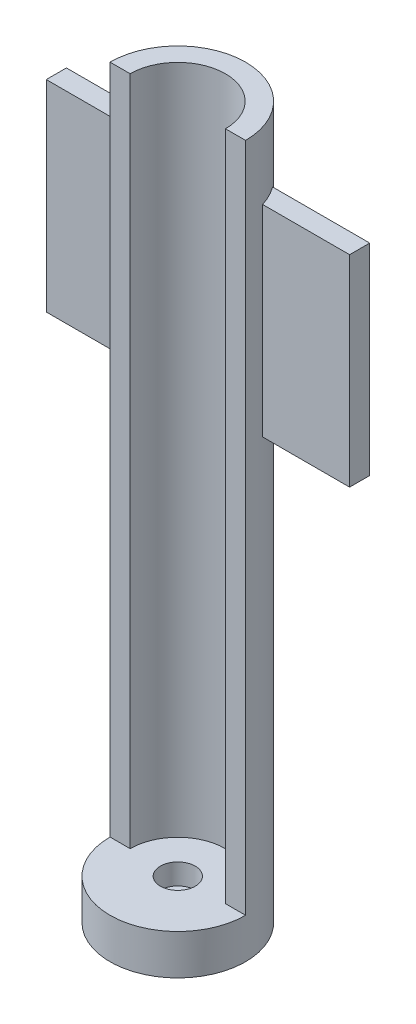
SolidWorks part; units mm, degrees
ref_plane "Front Plane" through (0, 0, 0) normal (0, 0, 1) x (1, 0, 0)
ref_plane "Top Plane" through (0, 0, 0) normal (0, 1, 0) x (1, 0, 0)
ref_plane "Right Plane" through (0, 0, 0) normal (1, 0, 0) x (0, 0, -1)
sketch "Sketch1" plane through (0, 0, 0) normal (0, 1, 0) x (1, 0, 0)
  circle A0 centre (0, 0) radius 7.1
  circle A1 centre (0, 0) radius 10.1
  dimension "D1" = 3
  dimension "D2" = 14.2
extrude "Boss-Extrude1" add sketch "Sketch1" along normal mid plane 100
sketch "Sketch2" plane through (0, -50, 0) normal (0, -1, 0) x (1, 0, 0)
  circle A0 centre (0, 0) radius 11.1
sketch "Sketch3" plane through (0, 0, 0) normal (0, 0, 1) x (1, 0, 0)
  line L1 (-101.5851, -102.8012) -> (101.5851, -102.8012)
  line L2 (-101.5851, -102.8012) -> (-101.5851, 102.8012)
  line L3 (-101.5851, 102.8012) -> (101.5851, 102.8012)
  line L4 (101.5851, -102.8012) -> (101.5851, 102.8012)
  line L5 (-101.5851, -102.8012) -> (101.5851, 102.8012) construction
  line L6 (-101.5851, 102.8012) -> (101.5851, -102.8012) construction
  point P0 (0, 0)
extrude "Cut-Extrude1" cut sketch "Sketch3" along normal through all
sketch "Sketch4" plane through (0, -50, 0) normal (0, -1, 0) x (1, 0, 0)
  circle A0 centre (0, 0) radius 10.1
  dimension "D1" = 20.2
extrude "Boss-Extrude3" add sketch "Sketch4" along normal blind 6
sketch "Sketch5" plane through (0, -50, 0) normal (0, 1, 0) x (1, 0, 0)
  circle A0 centre (0, 0) radius 2.6
  dimension "D1" = 5.2
extrude "Cut-Extrude2" cut sketch "Sketch5" against normal blind 3.1
ref_plane "Plane2" through (0, 0, -4.5) normal (0, 0, 1) x (1, 0, 0)
sketch "Sketch6" plane through (0, 0, -4.5) normal (0, 0, 1) x (1, 0, 0)
  line L0 (0, 17.3633) -> (0, 69.1455) construction
  line L1 (10.1, 50) -> (7.1, 50) construction
  line L2 (7.6, 40) -> (22.6, 40)
  line L3 (7.6, 40) -> (7.6, 10)
  line L4 (7.6, 10) -> (22.6, 10)
  line L5 (22.6, 40) -> (22.6, 10)
  line L7 (-22.6, 40) -> (-22.6, 10)
  line L8 (-7.6, 10) -> (-22.6, 10)
  line L9 (-7.6, 40) -> (-7.6, 10)
  line L10 (-7.6, 40) -> (-22.6, 40)
  dimension "D1" = 10
  dimension "D2" = 30
  dimension "D3" = 7.6
  dimension "D4" = 15
extrude "Boss-Extrude4" add sketch "Sketch6" along normal mid plane 3
sketch "Sketch7" plane through (0, 0, -6) normal (0, 0, -1) x (-1, 0, 0)
  line L0 (15.3623, 40) -> (15.3623, 10) construction
  line L1 (8.1247, 40) -> (22.6, 40) construction
  line L2 (22.6, 10) -> (8.1247, 10) construction
  line L3 (0, 0) -> (0, 47.416) construction
  text T0 "A2N\r\n2mm mold" font "Century Gothic" height in points 11
extrude "Boss-Extrude5" add sketch "Sketch7" along normal blind 1.5
